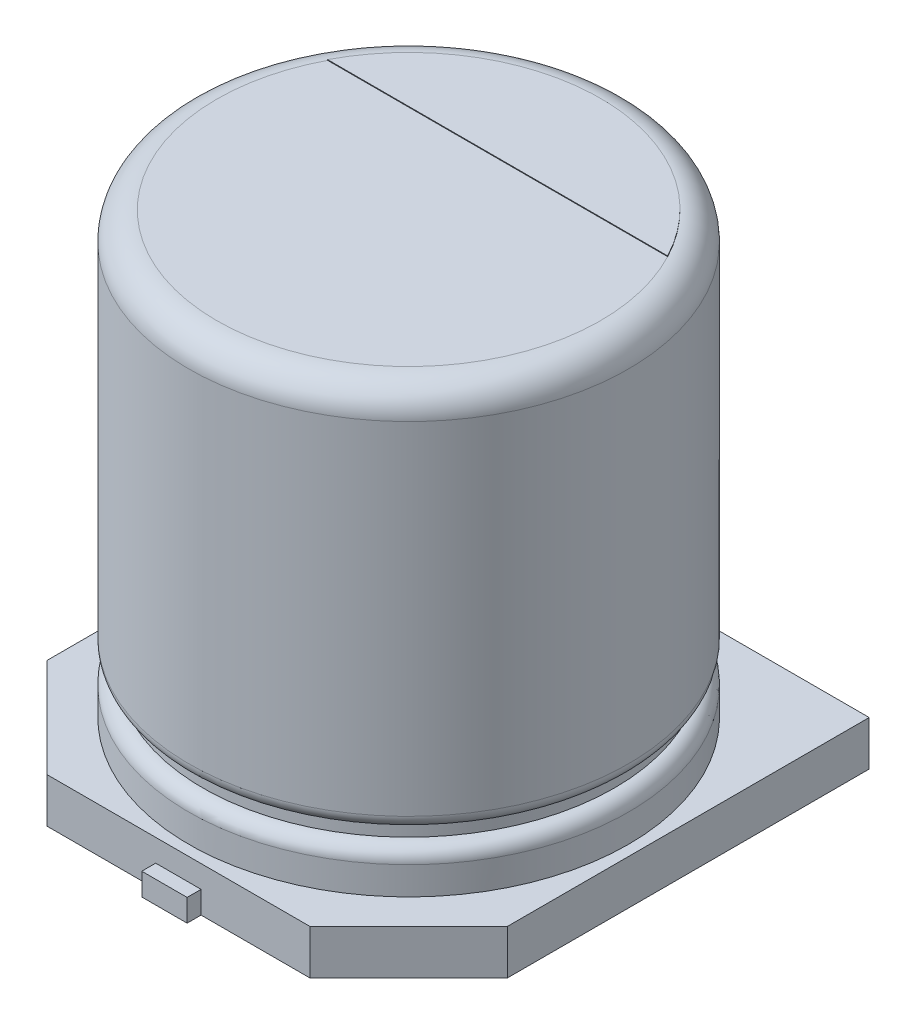
SolidWorks part; units mm, degrees
ref_plane "Front" through (0, 0, 0) normal (0, 0, 1) x (1, 0, 0)
ref_plane "Top" through (0, 0, 0) normal (0, 1, 0) x (1, 0, 0)
ref_plane "Right" through (0, 0, 0) normal (1, 0, 0) x (0, 0, -1)
sketch "Sketch1" plane through (0, 0, 0) normal (0, 0, 1) x (1, 0, 0)
  line L0 (0, 8.0822) -> (0, 0) construction
  line L1 (0, 6.3) -> (-2.75, 6.3)
  line L2 (-3.15, 5.9) -> (-3.15, 1)
  line L3 (-2.95, 0.8) -> (-2.95, 0.6)
  line L4 (-3.15, 0.4) -> (-3.15, 0)
  line L5 (-3.15, 0) -> (0, 0)
  line L6 (0, 0) -> (0, 6.3)
  line L7 (0, 0) -> (2.8151, 0) construction
  arc A0 (-2.75, 6.3) -> (-3.15, 5.9) centre (-2.75, 5.9) ccw
  arc A1 (-3.15, 1) -> (-2.95, 0.8) centre (-2.95, 1) ccw
  arc A2 (-2.95, 0.6) -> (-3.15, 0.4) centre (-2.95, 0.4) ccw
  dimension "D2" = 0.4
  dimension "D3" = 0.2
  dimension "D6" = 0.4
  dimension "D1" = 6.3
  dimension "D4" = 0.2
  dimension "D5" = 6.3
revolve "Revolve1" add sketch "Sketch1" angle 360 about L0
sketch "Sketch2" plane through (0, 6.3, 0) normal (0, 1, 0) x (1, 0, 0)
  line L0 (0, 0) -> (0, 2.75) construction
  line L1 (-2.4366, 1.275) -> (2.4366, 1.275)
  circle A0 centre (0, 0) radius 2.75 construction
  arc A1 (2.4366, 1.275) -> (-2.4366, 1.275) centre (0, 0) ccw
  dimension "D1" = 1.475
extrude "Boss-Extrude1" add sketch "Sketch2" along normal blind 0.01
sketch "Sketch3" plane through (0, 0, 0) normal (0, -1, 0) x (-1, 0, 0)
  line L0 (0, 0.9) -> (0, 0) construction
  line L1 (0, 0) -> (0.9284, 0) construction
  line L28 (1.8858, -3.3) -> (3.3, -1.8858)
  line L29 (3.3, -1.8858) -> (3.3, 3.3)
  line L31 (0.325, 3.3) -> (0.325, 0.9)
  line L32 (0.325, 0.9) -> (-0.325, 0.9)
  line L33 (-0.325, 0.9) -> (-0.325, 3.3)
  line L34 (3.3, 3.3) -> (-3.3, 3.3)
  line L35 (-3.3, 3.3) -> (-3.3, -1.8858)
  line L36 (-3.3, -1.8858) -> (-1.8858, -3.3)
  line L37 (-1.8858, -3.3) -> (1.8858, -3.3)
  line L38 (-0.325, -3.3) -> (-0.325, -0.9)
  line L39 (-0.325, -0.9) -> (0.325, -0.9)
  line L40 (0.325, -0.9) -> (0.325, -3.3)
  circle M43 centre (0, 0) radius 3.15
  dimension "D1" = 1.8
  dimension "D2" = 6.6
  dimension "D3" = 6.6
  dimension "D4" = 0.65
  dimension "D5" = 2
  dimension "D6" = 45
extrude "Boss-Extrude2" add sketch "Sketch3" along normal blind 0.64 contours L34 L35 L36 L37 L28 L29
extrude "Cut-Extrude1" cut sketch "Sketch3<3>" against normal blind 0.32 from vertex contours L33 L32 L31 M43 | L40 L39 L38 M43 | L31 L34 L33 M43 | L40 L38 L37 M43 region at (0, 0, 3.2221) region at (0, 0, 2.0222) region at (0, 0, -3.2221) region at (0, 0, -2.0222) starting at point (-3.3, -0.64, -3.3)
sketch "Sketch3<3>" plane through (0, 0, 0) normal (0, -1, 0) x (-1, 0, 0) same geometry as "Sketch3"
sketch "Sketch4" plane through (0, -0.32, 0) normal (0, -1, 0) x (1, 0, 0)
  line L0 (0.325, -0.9) -> (0.325, -3.3) construction
  line L1 (-0.325, -0.9) -> (0.325, -0.9)
  line L2 (-0.325, -0.9) -> (-0.325, -3.5)
  line L3 (-0.325, -3.5) -> (0.325, -3.5)
  line L4 (0.325, -0.9) -> (0.325, -3.5)
  line L5 (0, 0) -> (4.1796, 0) construction
  line L6 (-0.325, 0.9) -> (-0.325, 3.5)
  line L7 (-0.325, 0.9) -> (0.325, 0.9)
  line L8 (0.325, 0.9) -> (0.325, 3.5)
  line L9 (-0.325, 3.5) -> (0.325, 3.5)
  dimension "D1" = 2.6
extrude "Boss-Extrude3" add sketch "Sketch4" along normal blind 0.32
split line "Split Line1"
sketch "Sketch4<2>" plane through (0, -0.32, 0) normal (0, -1, 0) x (1, 0, 0) same geometry as "Sketch4"
